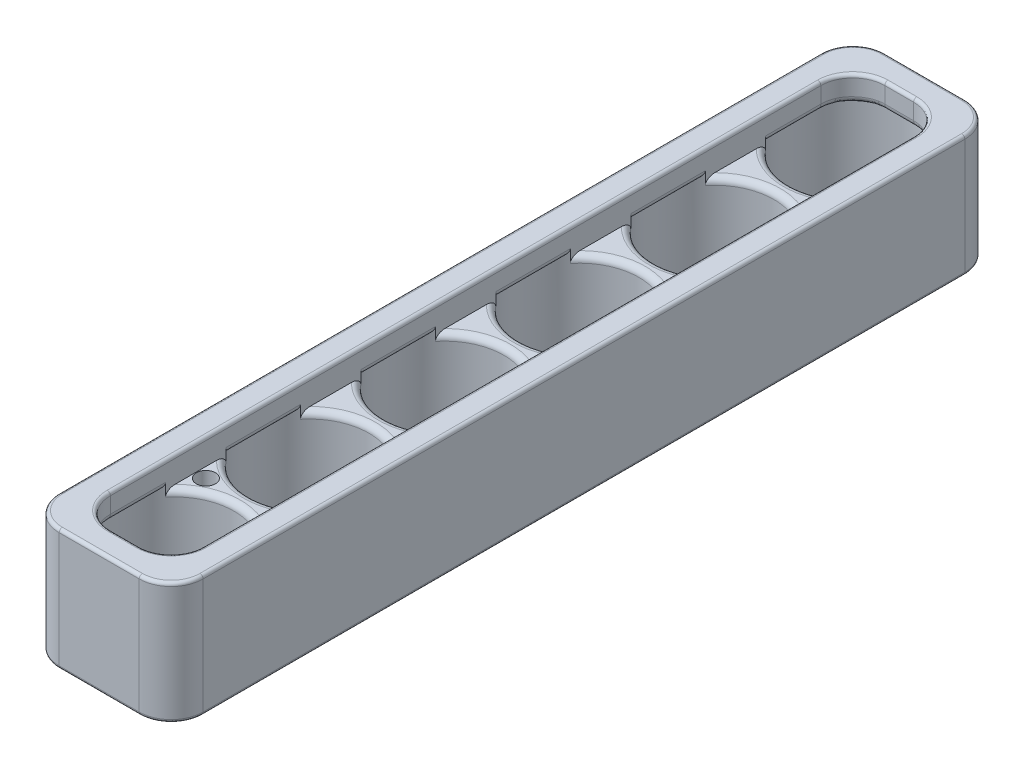
SolidWorks part; units mm, degrees
ref_plane "Front Plane" through (0, 0, 0) normal (0, 0, 1) x (1, 0, 0)
ref_plane "Top Plane" through (0, 0, 0) normal (0, 1, 0) x (1, 0, 0)
ref_plane "Right Plane" through (0, 0, 0) normal (1, 0, 0) x (0, 0, -1)
sketch "Esquisse1" plane through (0, 0, 0) normal (0, 1, 0) x (1, 0, 0)
  line L0 (0, 64.5) -> (0, -64.5) construction
  line L1 (-11.25, 64.5) -> (11.25, 64.5)
  line L2 (-11.25, 64.5) -> (-11.25, -64.5)
  line L3 (-11.25, -64.5) -> (11.25, -64.5)
  line L4 (11.25, 64.5) -> (11.25, -64.5)
  line L5 (-11.25, 64.5) -> (11.25, -64.5) construction
  line L6 (-11.25, -64.5) -> (11.25, 64.5) construction
  line L7 (0, -1.242) -> (0, 0) construction
  circle A0 centre (0, -10.542) radius 9.3
  circle A1 centre (0, -31.6277) radius 9.3
  circle A2 centre (0, -52.7134) radius 9.3
  circle A3 centre (0, -10.542) radius 9.3
  circle A4 centre (0, -31.6277) radius 9.3
  circle A5 centre (0, 10.5437) radius 9.3
  circle A6 centre (0, -10.542) radius 9.3
  circle A7 centre (0, 31.6294) radius 9.3
  circle A8 centre (0, 10.5437) radius 9.3
  circle A9 centre (0, 10.5437) radius 9.3
  circle A10 centre (0, 31.6294) radius 9.3
  circle A11 centre (0, 52.7151) radius 9.3
  point P0 (0, 0)
  dimension "D3" = 18.6
  dimension "D1" = 129
  dimension "D2" = 22.5
  dimension "D4" = 1.242
  dimension "D5" = 3
  dimension "D6" = 4
extrude "Boss.-Extru.1" add sketch "Esquisse1" along normal blind 19 contours L4 L1 L2 L3 A11 A7 A5 A2 A1 A0 region at (0, 0, 0.0011)
sketch "Esquisse2" plane through (0, 0, 64.5) normal (0, 0, 1) x (1, 0, 0)
  line L0 (-11.25, 19) -> (11.25, 19) construction
  line L1 (-7.25, 19) -> (7.25, 19)
  line L2 (-7.25, 19) -> (-7.25, 15)
  line L3 (-7.25, 15) -> (7.25, 15)
  line L4 (7.25, 19) -> (7.25, 15)
  line L5 (-11.25, 19) -> (-11.25, 0) construction
  line L6 (11.25, 19) -> (11.25, 0) construction
  dimension "D1" = 4
  dimension "D2" = 4
  dimension "D3" = 4
extrude "Enlèv. mat.-Extru.1" cut sketch "Esquisse2" against normal through all both and the other way through all
sketch "Esquisse3" plane through (0, 19, 0) normal (0, 1, 0) x (1, 0, 0)
  line L1 (11.25, 64.5) -> (7.25, 64.5)
  line L2 (11.25, 64.5) -> (11.25, -64.5)
  line L3 (11.25, -64.5) -> (7.25, -64.5)
  line L4 (7.25, 64.5) -> (7.25, -64.5)
  line L5 (-7.25, -64.5) -> (-11.25, -64.5)
  line L6 (-7.25, -64.5) -> (-7.25, 64.5)
  line L7 (-7.25, 64.5) -> (-11.25, 64.5)
  line L8 (-11.25, -64.5) -> (-11.25, 64.5)
extrude "Boss.-Extru.2" add sketch "Esquisse3" against normal up to surface (4 mm away) up to face at (0, 15, 62.3879)
sketch "Esquisse4" plane through (0, 19, 0) normal (0, 1, 0) x (1, 0, 0)
  line L0 (11.25, 64.5) -> (11.25, -64.5) construction
  line L1 (-11.25, 64.5) -> (11.25, 64.5)
  line L2 (-11.25, 64.5) -> (-11.25, 60.5)
  line L3 (-11.25, 60.5) -> (11.25, 60.5)
  line L4 (11.25, 64.5) -> (11.25, 60.5)
  line L6 (-11.25, -64.5) -> (11.25, -64.5)
  line L7 (-11.25, -64.5) -> (-11.25, -60.5)
  line L8 (-11.25, -60.5) -> (11.25, -60.5)
  line L9 (11.25, -64.5) -> (11.25, -60.5)
  dimension "D1" = 4
  dimension "D2" = 4
extrude "Boss.-Extru.3" add sketch "Esquisse4" against normal up to surface (4 mm away) up to face at (0, 15, -42.1723)
fillet "Congé1" radius 5 4 edges at (-7.25, 17, 60.5) (7.25, 17, 60.5) (-7.25, 17, -60.5) (7.25, 17, -60.5)
fillet "Congé2" radius 5 4 edges at (-11.25, 9.5, -64.5) (11.25, 9.5, -64.5) (11.25, 9.5, 64.5) (-11.25, 9.5, 64.5)
fillet "Congé3" radius 0.5 30 edges at (-5.7855, 19, -59.0355) (0, 19, -60.5) (5.7855, 19, -59.0355) (7.25, 19, 0) (5.7855, 19, 59.0355) (0, 19, 60.5) (-5.7855, 19, 59.0355) (9.7855, 19, -63.0355) (0, 19, -64.5) (-9.7855, 19, -63.0355) (-11.25, 19, 0) (-9.7855, 19, 63.0355) (0, 19, 64.5) (9.7855, 19, 63.0355) (9.7855, 0, -63.0355) (0, 0, -64.5) (-9.7855, 0, -63.0355) (-11.25, 0, 0) (-9.7855, 0, 63.0355) (0, 0, 64.5) (9.7855, 0, 63.0355) (-7.25, 19, 0) (11.25, 19, 0) (0, 0, 62.0134) (0, 0, 40.9277) (0, 0, 19.842) (0, 0, -1.2437) (0, 0, -22.3294) (0, 0, -43.4151) (11.25, 0, 0)
fillet "Congé6" radius 1 16 edges at (7.25, 15, 51.1943) (5.7855, 15, 59.0355) (0, 15, 60.5) (-5.7855, 15, 59.0355) (-7.25, 15, 51.1943) (-5.7855, 15, -59.0355) (0, 15, -60.5) (5.7855, 15, -59.0355) (7.25, 15, -31.6294) (7.25, 15, -10.5437) (7.25, 15, 10.542) (7.25, 15, 31.6277) (-7.25, 15, 31.6277) (-7.25, 15, 10.542) (-7.25, 15, -10.5437) (-7.25, 15, -31.6294)
fillet "Congé7" radius 1 10 edges at (0, 15, 43.4134) (0, 15, 40.9277) (0, 15, 22.3277) (0, 15, 19.842) (0, 15, 1.242) (0, 15, -1.2437) (0, 15, -19.8437) (0, 15, -22.3294) (0, 15, -40.9294) (0, 15, -43.4151)
sketch "Esquisse5" plane through (0, 15, 0) normal (0, 1, 0) x (1, 0, 0)
  line L0 (-7.25, -42.1705) -> (-5.6535, -42.1705) construction
  line L1 (-7.25, -38.9439) -> (-7.25, -45.3972) construction
  circle A0 centre (-5.6535, -42.1705) radius 1.5
  dimension "D1" = 3
  dimension "D2" = 1.5965
extrude "Enlèv. mat.-Extru.2" cut sketch "Esquisse5" against normal through all
